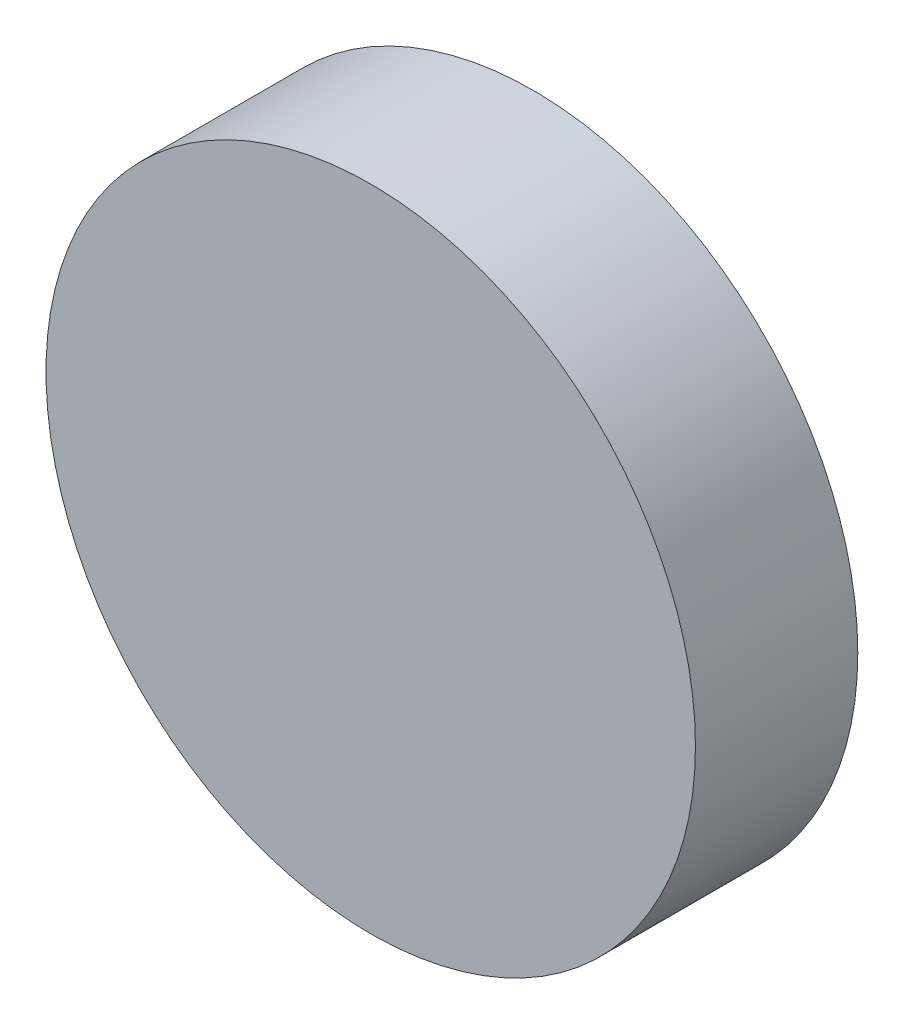
SolidWorks part; units mm, degrees
ref_plane "Спереди" through (0, 0, 0) normal (0, 0, 1) x (1, 0, 0)
ref_plane "Сверху" through (0, 0, 0) normal (0, 1, 0) x (1, 0, 0)
ref_plane "Справа" through (0, 0, 0) normal (1, 0, 0) x (0, 0, -1)
other "Configuration Table"
sketch "Эскиз1" plane through (0, 0, 0) normal (0, 0, 1) x (1, 0, 0)
  circle A0 centre (0, 0) radius 80
extrude "Колесо Ø160 × 40 (упрощено)" add sketch "Эскиз1" along normal blind 20 and the other way blind 20
